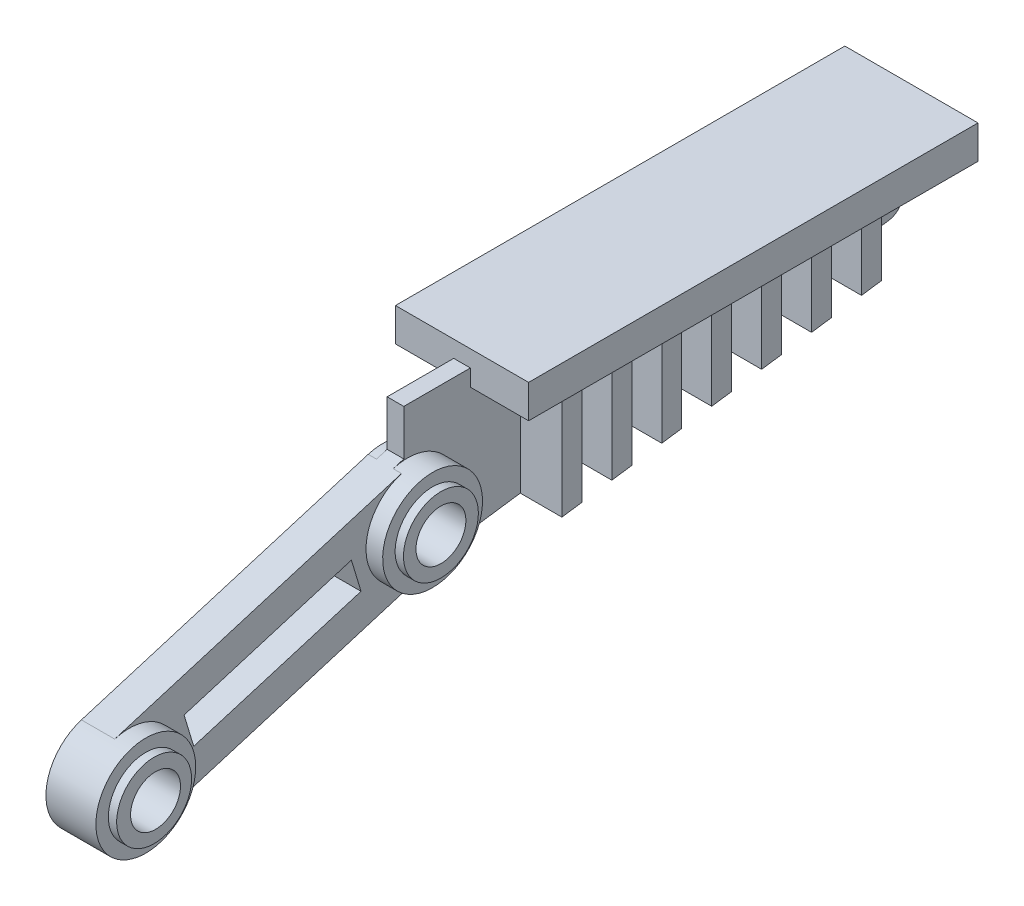
SolidWorks part; units mm, degrees
note: '?' marks a value the reader was unsure of.
material "ABS"
ref_plane "Front Plane" through (0, 0, 0) normal (0, 0, 1) x (1, 0, 0)
ref_plane "Top Plane" through (0, 0, 0) normal (0, 1, 0) x (1, 0, 0)
ref_plane "Right Plane" through (0, 0, 0) normal (1, 0, 0) x (0, 0, -1)
sketch "Sketch1" plane through (0, 0, 0) normal (0, 1, 0) x (1, 0, 0)
  line L1 (-4, 13.5) -> (4, 13.5)
  line L2 (-4, 13.5) -> (-4, -13.5)
  line L3 (-4, -13.5) -> (4, -13.5)
  line L4 (4, 13.5) -> (4, -13.5)
  line L5 (-4, 13.5) -> (4, -13.5) construction
  line L6 (-4, -13.5) -> (4, 13.5) construction
  point P0 (0, 0)
  dimension "D1" = 8
  dimension "D2" = 27
extrude "Boss-Extrude1" add sketch "Sketch1" against normal blind 2
sketch "Sketch4" plane through (0, 0, 0) normal (1, 0, 0) x (0, 0, -1)
  line L0 (13.5, 0) -> (13.5, -2)
  line L1 (13.5, -2) -> (12.2639, -5.8042)
  line L2 (12.2639, -5.8042) -> (-17.5, -10)
  line L3 (13.5, -2) -> (-13.5, -2) construction
  line L4 (13.5, 0) -> (-13.5, 0)
  line L5 (4.4, 0) -> (-4.4, 0) construction
  line L6 (-13.5, 0) -> (-13.5, -1)
  line L7 (-13.5, -1) -> (-17.5, -1)
  line L8 (-17.5, -10) -> (-19.2346, -4.2562) construction
  line L9 (-17.5, -1) -> (-17.5, -10) construction
  line L10 (-17.5, -10) -> (-33.6327, -14.8719)
  line L11 (-19.2346, -4.2562) -> (-35.3673, -9.1281)
  line L12 (-19.2346, -4.2562) -> (-17.5012, -3.7327)
  line L13 (-17.5012, -3.7327) -> (-17.5, -1)
  line L14 (-34.5, -12) -> (-17.2686, -6.7963) construction
  arc A0 (-35.3673, -9.1281) -> (-33.6327, -14.8719) centre (-34.5, -12) ccw
  dimension "D9" = 6
  dimension "D11" = 15
  dimension "D1" = 13.5
  dimension "D2" = 2
  dimension "D3" = 4
  dimension "D4" = 72
  dimension "D5" = 27
  dimension "D6" = 1
  dimension "D7" = 4
  dimension "D8" = 90
  dimension "D10" = 51
  dimension "D12" = 9
  dimension "D13" = 6
  dimension "D14" = 2.7327
  dimension "D15" = 18
extrude "Boss-Extrude2" add sketch "Sketch4" along normal mid plane 1
sketch "Sketch5" plane through (-0.5, 0, 0) normal (-1, 0, 0) x (0, 0, 1)
  line L0 (17.5012, -3.7327) -> (35.3673, -9.1281) construction
  line L1 (33.6327, -14.8719) -> (16.4223, -9.6745)
  line L2 (35.3673, -9.1281) -> (18.1359, -3.9244)
  arc A0 (33.6327, -14.8719) -> (35.3673, -9.1281) centre (34.5, -12) ccw
  arc A1 (18.1359, -3.9244) -> (16.4223, -9.6745) centre (17.2686, -6.7963) ccw
  arc M8 (33.6327, -14.8719) -> (35.3673, -9.1281) centre (34.5, -12) ccw
  line M9 (35.3673, -9.1281) -> (17.5012, -3.7327)
  dimension "D2" = 6
  dimension "D3" = 0
  dimension "D4" = 18
extrude "Boss-Extrude3" add sketch "Sketch5" along normal blind 0.5 contours A1 L1 M9 M8
sketch "Sketch6" plane through (0.5, 0, 0) normal (1, 0, 0) x (0, 0, -1)
  line L0 (-17.5012, -3.7327) -> (-35.3673, -9.1281) construction
  line L1 (-35.3673, -9.1281) -> (-18.1359, -3.9244)
  line L2 (-33.6327, -14.8719) -> (-16.4013, -9.6682)
  arc A1 (-35.3673, -9.1281) -> (-33.6327, -14.8719) centre (-34.5, -12) ccw
  arc A2 (-16.4013, -9.6682) -> (-18.1359, -3.9244) centre (-17.2686, -6.7963) ccw
  dimension "D1" = 6
  dimension "D4" = 3
  dimension "D3" = 18
extrude "Boss-Extrude4" add sketch "Sketch6" along normal blind 0.5
sketch "Sketch7" plane through (-1, 0, 0) normal (-1, 0, 0) x (0, 0, 1)
  circle A0 centre (17.2686, -6.7963) radius 2.25
  dimension "D1" = 4.5
extrude "Boss-Extrude5" add sketch "Sketch7" along normal blind 0.5
sketch "Sketch8" plane through (1, 0, 0) normal (1, 0, 0) x (0, 0, -1)
  circle A0 centre (-34.5, -12) radius 3
  circle A1 centre (-17.2686, -6.7963) radius 3
  arc A2 (-16.4013, -9.6682) -> (-18.1359, -3.9244) centre (-17.2686, -6.7963) ccw construction
  dimension "D1" = 6
  dimension "D2" = 0
extrude "Boss-Extrude6" add sketch "Sketch8" along normal blind 1
sketch "Sketch9" plane through (2, 0, 0) normal (1, 0, 0) x (0, 0, -1)
  circle A0 centre (-34.5, -12) radius 2.25
  circle A1 centre (-17.2686, -6.7963) radius 2.25
  dimension "D1" = 4.5
  dimension "D2" = 4.5
extrude "Boss-Extrude7" add sketch "Sketch9" along normal blind 0.5
sketch "Sketch10" plane through (2.5, 0, 0) normal (1, 0, 0) x (0, 0, -1)
  circle A0 centre (-17.2686, -6.7963) radius 1.5
  circle A1 centre (-34.4157, -12.0513) radius 1.5
  dimension "D1" = 3
  dimension "D2" = 3
ref_axis "Axis2" through (1, -14.8719, 33.6327) along (0, 0.2891, -0.9573)?
ref_plane "Plane1" through (1, 0, 0) normal (-1, 0, 0) x (0, 0.2891, -0.9573)
sketch "Sketch14" plane through (1, 0, 0) normal (-1, 0, 0) x (0, 0.2891, -0.9573)
  line L0 (-18.496, -1.4861) -> (-36.496, -1.4861) construction
  line L1 (-22.246, 2.5139) -> (-32.746, 2.5139)
  line L2 (-22.246, 2.5139) -> (-22.246, 0.5139)
  line L3 (-22.246, 0.5139) -> (-32.746, 0.5139)
  line L4 (-32.746, 2.5139) -> (-32.746, 0.5139)
  line L5 (-22.246, 2.5139) -> (-32.746, 0.5139) construction
  line L6 (-22.246, 0.5139) -> (-32.746, 2.5139) construction
  point P0 (-27.496, 1.5139)
  dimension "D1" = 3
  dimension "D2" = 2
  dimension "D3" = 10.5
  dimension "D4" = 9
extrude "Cut-Extrude2" cut sketch "Sketch14" along normal blind 1.8
fillet "Fillet1" radius 1 1 edges at (0, -5.8042, -12.2639)
ref_axis "Axis3" through (-1, -14.8719, 33.6327) along (0, 0.2891, -0.9573)?
ref_plane "Plane2" through (-1, 0, 0) normal (1, 0, 0) x (0, 0.2891, -0.9573)
sketch "Sketch15" plane through (-1, 0, 0) normal (1, 0, 0) x (0, 0.2891, -0.9573)
  line L0 (-36.496, 1.4863) -> (-18.496, 1.4862) construction
  line L1 (-25.496, 0.2363) -> (-29.496, 0.2363)
  line L2 (-25.496, 0.2363) -> (-25.496, -3.2637)
  line L3 (-25.496, -3.2637) -> (-29.496, -3.2637)
  line L4 (-29.496, 0.2363) -> (-29.496, -3.2637)
  line L5 (-25.496, 0.2363) -> (-29.496, -3.2637) construction
  line L6 (-25.496, -3.2637) -> (-29.496, 0.2363) construction
  arc A0 (-36.496, 1.4863) -> (-36.496, -4.5137) centre (-36.496, -1.5137) ccw construction
  point P0 (-27.496, -1.5137)
  dimension "D1" = 3
  dimension "D2" = 3.5
  dimension "D3" = 4
  dimension "D4" = 9
extrude "Cut-Extrude5" cut sketch "Sketch15" along normal blind 0.1
sketch "Sketch19" plane through (0, -2, 0) normal (0, -1, 0) x (1, 0, 0)
  line L0 (0, -8.25) -> (0, 8.25) construction
  line L1 (-3, 9.3) -> (3, 9.3)
  line L2 (-3, 9.3) -> (-3, 10.5)
  line L3 (-3, 10.5) -> (3, 10.5)
  line L4 (3, 9.3) -> (3, 10.5)
  line L5 (-3, 9.3) -> (3, 10.5) construction
  line L6 (-3, 10.5) -> (3, 9.3) construction
  line L7 (-4, 13.5) -> (-0.5, 13.5) construction
  point P0 (0, 9.9)
  dimension "D1" = 6
  dimension "D2" = 1.2
  dimension "D3" = 3
extrude "Boss-Extrude8" add sketch "Sketch19" along normal blind 7.1
pattern_linear "LPattern1" count 7 spacing 3 along (0, 0, -1) of "Boss-Extrude8"
ref_axis "Axis4" through (0.5, -7.5753, 0.3) along (0, 0.1396, -0.9902)?
ref_plane "Plane3" through (0.5, 0, 0) normal (-1, 0, 0) x (0, 0.1396, -0.9902)
sketch "Sketch20" plane through (0.5, 0, 0) normal (-1, 0, 0) x (0, 0.1396, -0.9902)
  line L1 (7.7345, 7.4593) -> (-12.2449, 7.4593)
  line L2 (7.7345, 7.4593) -> (7.7345, 10.8806)
  line L3 (7.7345, 10.8806) -> (-12.2449, 10.8806)
  line L4 (-12.2449, 7.4593) -> (-12.2449, 10.8806)
extrude "Cut-Extrude6" cut sketch "Sketch20" against normal mid plane 7.1
extrude "Cut-Extrude7" cut sketch "Sketch10" against normal through all
sketch "Sketch21" plane through (-0.8, 0, 0) normal (1, 0, 0) x (0, 0, -1)
  line L0 (-30.621, -11.8732) -> (-27.6956, -9.1452) construction
  line L1 (-30.621, -11.8732) -> (-31.1992, -9.9586) construction
  line L2 (-20.5694, -8.8377) -> (-30.621, -11.8732) construction
  line L3 (4.4, 0) -> (-4.4, 0) construction
  line L4 (-27.6956, -9.1452) -> (-29.1583, -10.5092)
  line L5 (-27.6956, -9.1452) -> (-27.3546, -9.5109)
  line L6 (-29.1583, -10.5092) -> (-28.8173, -10.8749)
  line L7 (-27.3546, -9.5109) -> (-28.8173, -10.8749)
  dimension "D1" = 43
  dimension "D2" = 0.5
  dimension "D4" = 4
extrude "Boss-Extrude9" add sketch "Sketch21" along normal blind 0.5 contours L4 L6 L7 L5
sketch "Sketch22" plane through (-1, 0, 0) normal (-1, 0, 0) x (0, 0, 1)
  point P0 (17.2686, -6.7963)
  point P1 (-5.7314, 14.2037)
  dimension "D1" = 23
  dimension "D2" = 21
ref_plane "LH_GripPanel" through (0, 4.8923, 4.4668) normal (0, 0.7385, 0.6743) x (1, 0, 0)
equation "\"D2@Sketch9\"=\"D1@Sketch9\""
equation "\"D2@Sketch10\"=\"D1@Sketch10\""
